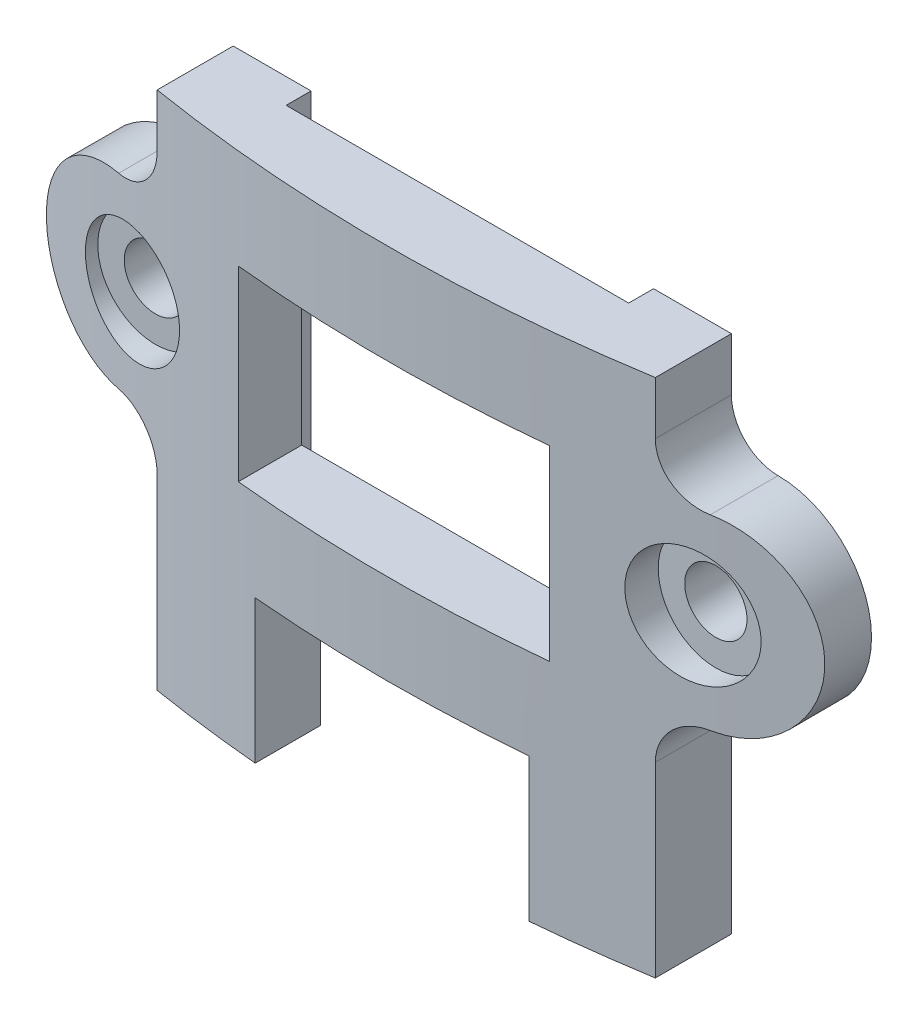
SolidWorks part; units mm, degrees
ref_plane "Front Plane" through (0, 0, 0) normal (0, 0, 1) x (1, 0, 0)
ref_plane "Top Plane" through (0, 0, 0) normal (0, 1, 0) x (1, 0, 0)
ref_plane "Right Plane" through (0, 0, 0) normal (1, 0, 0) x (0, 0, -1)
sketch "Sketch1" plane through (0, 0, 0) normal (0, 0, 1) x (1, 0, 0)
  line L1 (5.5, -8.35) -> (-5.5, -8.35)
  line L2 (5.5, -8.35) -> (5.5, 8.35)
  line L3 (5.5, 8.35) -> (-5.5, 8.35)
  line L4 (-5.5, -8.35) -> (-5.5, 8.35)
  line L5 (5.5, -8.35) -> (-5.5, 8.35) construction
  line L6 (5.5, 8.35) -> (-5.5, -8.35) construction
  line L7 (5, -0.85) -> (-5, -0.85)
  line L8 (5, -0.85) -> (5, 5.15)
  line L9 (5, 5.15) -> (-5, 5.15)
  line L10 (-5, -0.85) -> (-5, 5.15)
  line L11 (5, -0.85) -> (-5, 5.15) construction
  line L12 (5, 5.15) -> (-5, -0.85) construction
  line L13 (4.4, -7.75) -> (-4.4, -7.75)
  line L14 (4.4, -7.75) -> (4.4, -3.75)
  line L15 (4.4, -3.75) -> (-4.4, -3.75)
  line L16 (-4.4, -7.75) -> (-4.4, -3.75)
  line L17 (4.4, -7.75) -> (-4.4, -3.75) construction
  line L18 (4.4, -3.75) -> (-4.4, -7.75) construction
  point P0 (0, 0)
  point P6 (0, 2.15)
  point P11 (0, -5.75)
  point P16 (4.4, -5.75)
  dimension "D1" = 16.7
  dimension "D2" = 11
  dimension "D3" = 10.5
  dimension "D4" = 6
  dimension "D5" = 10
  dimension "D6" = 4
  dimension "D7" = 1.1
  dimension "D8" = 0.6
sketch "Sketch2" plane through (0, 0, 0) normal (0, 0, 1) x (1, 0, 0)
  line L0 (-4.4, -8.35) -> (-8, -8.35)
  line L1 (-8, -8.35) -> (-8, 8.35)
  line L2 (-8, 8.35) -> (8, 8.35)
  line L3 (8, 8.35) -> (8, -8.35)
  line L4 (8, -8.35) -> (4.4, -8.35)
  line L5 (4.4, -8.35) -> (4.4, -3.75)
  line L6 (4.4, -3.75) -> (-4.4, -3.75)
  line L7 (-4.4, -3.75) -> (-4.4, -8.35)
  line L8 (5.5, 8.35) -> (-5.5, 8.35) construction
  line L9 (5.5, -8.35) -> (-5.5, -8.35) construction
  point P5 (0, 8.35)
  dimension "D1" = 16
  dimension "D2" = 16.7
extrude "main" add sketch "Sketch2" along normal blind 5.1
extrude "sensor_cut" cut sketch "Sketch1" along normal up to surface (5.1 mm away) contours L9 L10 L7 L8 up to face at (0, -3.025, 5.1)
sketch "Sketch3" plane through (0, 0, 0) normal (0, 0, -1) x (-1, 0, 0)
  line L0 (-8, 2.15) -> (8, 2.15) construction
  line L1 (-8, -8.35) -> (-8, 8.35) construction
  line L2 (8, 8.35) -> (8, -8.35) construction
  line L3 (0, 8.35) -> (0, -8.35) construction
  line L4 (-8, 8.35) -> (8, 8.35) construction
  line L5 (9.5, -0.85) -> (8, -0.85)
  line L6 (8, -0.85) -> (8, 5.15)
  line L7 (8, 5.15) -> (9.5, 5.15)
  line L8 (-5, -0.85) -> (5, -0.85) construction
  line L9 (-8, 5.15) -> (-9.5, 5.15)
  line L10 (-8, -0.85) -> (-8, 5.15)
  line L11 (-9.5, -0.85) -> (-8, -0.85)
  arc A0 (9.5, 5.15) -> (9.5, -0.85) centre (9.5, 2.15) cw
  arc A3 (-9.5, 5.15) -> (-9.5, -0.85) centre (-9.5, 2.15) ccw
  point P6 (8, 5.15)
  point P20 (0, 2.15)
  dimension "D4" = 3
  dimension "D1" = 6
  dimension "D3" = 1.5
extrude "mounting_ears" add sketch "Sketch3" against normal blind 3
sketch "Sketch4" plane through (0, 0, 3) normal (0, 0, 1) x (1, 0, 0)
  line L0 (-8, 8.35) -> (-8, -8.35) construction
  circle A0 centre (-9, 2.15) radius 1
  dimension "D1" = 2
  dimension "D2" = 1
extrude "mount_holes" cut sketch "Sketch4" against normal up to surface (3 mm away) up to face at (0, -0.4375, 0)
sketch "Sketch9" plane through (0, 0, 3) normal (0, 0, 1) x (1, 0, 0)
  circle A0 centre (-9, 2.15) radius 1.85
  point P0 (-9, 2.15)
  dimension "D1" = 3.7
extrude "Cut-Extrude1" cut sketch "Sketch9" against normal blind 1.5
mirror "Mirror1" about plane through (0, 0, 0) normal (1, 0, 0) of "mount_holes", "Cut-Extrude1"
sketch "Sketch5" plane through (0, 8.35, 0) normal (0, 1, 0) x (1, 0, 0)
  line L0 (8, 0) -> (-8, 0) construction
  line L1 (-9.5, 0) -> (-12.5, 0) construction
  line L5 (-12.5, -1.5) -> (-12.5, -9.9232)
  line L6 (12.5, -3) -> (12.5, 0) construction
  line L7 (-12.5, 0) -> (-12.5, -3) construction
  line L8 (-12.5, -9.9232) -> (12.5, -9.9232)
  line L9 (12.5, -9.9232) -> (12.5, -1.5)
  arc A1 (-12.5, -1.5) -> (12.5, -1.5) centre (0, 46.9123) ccw
  dimension "D1" = 50
  dimension "D2" = 1.5
  dimension "D3" = 1.5
extrude "circular_front_cut" cut sketch "Sketch5" against normal up to surface (16.7 mm away) up to face at (-6.2, -8.35, 2.55)
sketch "Sketch6" plane through (0, 0, 0) normal (0, 0, -1) x (-1, 0, 0)
  line L0 (-8, 8.35) -> (8, 8.35) construction
  line L1 (5.5, -8.35) -> (-5.5, -8.35)
  line L2 (5.5, -8.35) -> (5.5, 8.35)
  line L3 (5.5, 8.35) -> (-5.5, 8.35)
  line L4 (-5.5, -8.35) -> (-5.5, 8.35)
  line L5 (5.5, -8.35) -> (-5.5, 8.35) construction
  line L6 (5.5, 8.35) -> (-5.5, -8.35) construction
  point P0 (0, 0)
  dimension "D1" = 11
extrude "pcb_cut" cut sketch "Sketch6" against normal blind 0.8
fillet "Fillet3" radius 1.5 4 edges at (-8, -0.85, 1.2218) (-8, 5.15, 1.2218) (8, 5.15, 1.2218) (8, -0.85, 1.2218)
